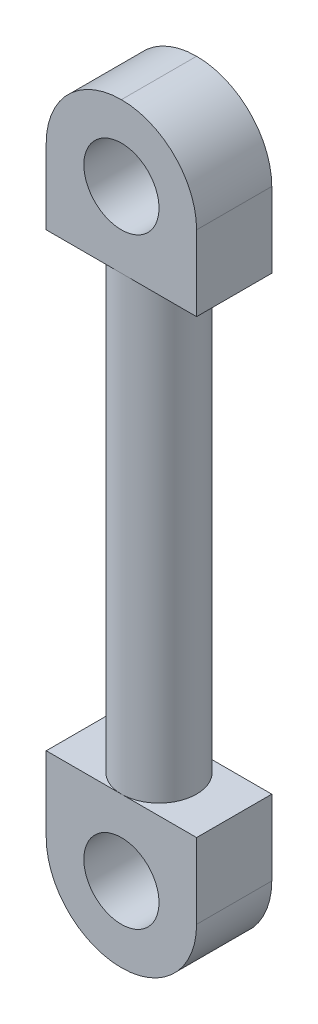
SolidWorks part; units mm, degrees
ref_plane "Front Plane" through (0, 0, 0) normal (0, 0, 1) x (1, 0, 0)
ref_plane "Top Plane" through (0, 0, 0) normal (0, 1, 0) x (1, 0, 0)
ref_plane "Right Plane" through (0, 0, 0) normal (1, 0, 0) x (0, 0, -1)
sketch "Sketch1" plane through (0, 0, 0) normal (0, 1, 0) x (1, 0, 0)
  circle A0 centre (0, 0) radius 1.5875
  dimension "D1" = 3.175
extrude "Boss-Extrude1" add sketch "Sketch1" along normal blind 9.525
sketch "Sketch2" plane through (0, 9.525, 0) normal (0, 1, 0) x (1, 0, 0)
  line L1 (-3.175, -1.5875) -> (3.175, -1.5875)
  line L2 (-3.175, -1.5875) -> (-3.175, 1.5875)
  line L3 (-3.175, 1.5875) -> (3.175, 1.5875)
  line L4 (3.175, -1.5875) -> (3.175, 1.5875)
  line L5 (-3.175, -1.5875) -> (3.175, 1.5875) construction
  line L6 (-3.175, 1.5875) -> (3.175, -1.5875) construction
  circle A0 centre (0, 0) radius 1.5875 construction
  point P0 (0, 0)
  dimension "D1" = 6.35
extrude "Boss-Extrude2" add sketch "Sketch2" along normal blind 6.35
sketch "Sketch3" plane through (0, 0, -1.5875) normal (0, 0, -1) x (-1, 0, 0)
  line L0 (-3.175, 15.875) -> (3.175, 15.875) construction
  circle A0 centre (0, 12.7) radius 1.5875
  dimension "D1" = 3.175
  dimension "D2" = 3.175
extrude "Cut-Extrude1" cut sketch "Sketch3" against normal through all
mirror "Mirror1" about plane through (0, 0, 0) normal (0, 1, 0) of "Boss-Extrude1", "Cut-Extrude1", "Boss-Extrude2"
fillet "Fillet1" radius 3.175 4 edges at (-3.175, -15.875, 0) (3.175, -15.875, 0) (-3.175, 15.875, 0) (3.175, 15.875, 0)
